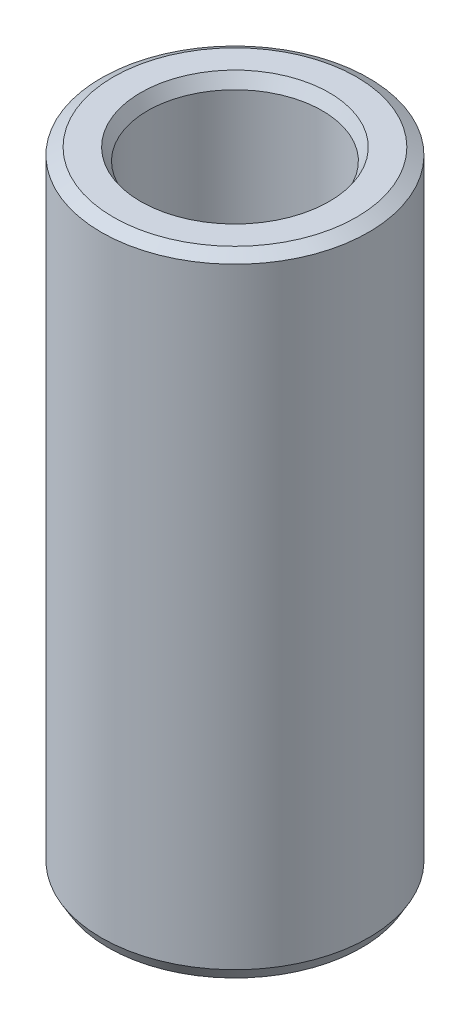
SolidWorks part; units mm, degrees
ref_plane "Front Plane" through (0, 0, 0) normal (0, 0, 1) x (1, 0, 0)
ref_plane "Top Plane" through (0, 0, 0) normal (0, 1, 0) x (1, 0, 0)
ref_plane "Right Plane" through (0, 0, 0) normal (1, 0, 0) x (0, 0, -1)
sketch "Sketch1" plane through (0, 0, 0) normal (0, 1, 0) x (1, 0, 0)
  circle A0 centre (0, 0) radius 10
  dimension "SLEEVE_OD" = 20
extrude "Boss-Extrude1" add sketch "Sketch1" along normal blind 47.1369
sketch "Sketch2" plane through (0, 0, 0) normal (0, 1, 0) x (1, 0, 0)
  circle A0 centre (0, 0) radius 6.5333
  dimension "BORE_D" = 13.0666
extrude "Cut-Extrude1" cut sketch "Sketch2" along normal through all
chamfer "Chamfer1" distance 0.5228 angle 60 4 edges at (0, 47.1369, 6.5333) (0, 0, 6.5333) (0, 0, 10) (0, 47.1369, 10) first distance on face at (0, 47.1369, 6.5333) first distance on face at (0, 0, 6.5333) first distance on face at (0, 47.1369, 10)
